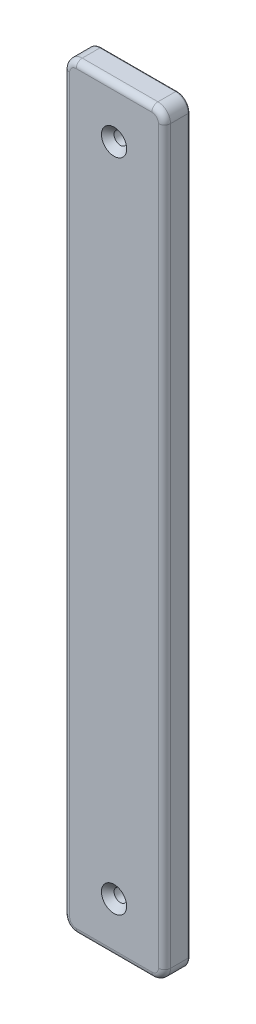
SolidWorks part; units mm, degrees
ref_plane "Front" through (0, 0, 0) normal (0, 0, 1) x (1, 0, 0)
ref_plane "Top" through (0, 0, 0) normal (0, 1, 0) x (1, 0, 0)
ref_plane "Right" through (0, 0, 0) normal (1, 0, 0) x (0, 0, -1)
sketch "Sketch1" plane through (0, 0, 0) normal (0, 0, 1) x (1, 0, 0)
  line L0 (0, 190.5) -> (0, -190.5) construction
  line L1 (25.4, -190.5) -> (-25.4, -190.5)
  line L2 (25.4, -190.5) -> (25.4, 190.5)
  line L3 (-25.4, 190.5) -> (25.4, 190.5)
  line L4 (-25.4, 190.5) -> (-25.4, -190.5)
  dimension "D1" = 381
  dimension "D3" = 50.8
extrude "Base-Extrude" add sketch "Sketch1" along normal blind 12.7
sketch "Sketch2" plane through (0, 0, 12.7) normal (0, 0, 1) x (1, 0, 0)
  line L0 (0, 0) -> (71.1, 0) construction
  line L1 (0, 190.5) -> (0, -190.5) construction
  line L2 (-25.4, 190.5) -> (25.4, 190.5) construction
  line L3 (25.4, -190.5) -> (-25.4, -190.5) construction
  circle A1 centre (0, -165.1) radius 3.175
  circle A3 centre (0, 165.1) radius 3.175
  dimension "D2" = 6.35
  dimension "D1" = 330.2
extrude "Cut-Extrude1" cut sketch "Sketch2" against normal through all
chamfer "Chamfer1" distance 3.175 angle 45 2 edges at (3.175, 165.1, 12.7) (3.175, -165.1, 12.7)
fillet "Fillet1" radius 6.35 4 edges at (25.4, -190.5, 6.35) (-25.4, -190.5, 6.35) (-25.4, 190.5, 6.35) (25.4, 190.5, 6.35)
fillet "Fillet2" radius 3.048 8 edges at (-23.5401, 188.6401, 12.7) (0, 190.5, 12.7) (23.5401, 188.6401, 12.7) (25.4, 0, 12.7) (23.5401, -188.6401, 12.7) (0, -190.5, 12.7) (-23.5401, -188.6401, 12.7) (-25.4, 0, 12.7)
shell "Shell1" thickness 1.524
ref_plane "Plane1" through (0, 0, 1.524) normal (0, 0, -1) x (-1, 0, 0)
sketch "Sketch3" plane through (0, 0, 1.524) normal (0, 0, -1) x (-1, 0, 0)
  line L0 (0, 165.1) -> (0, -165.1)
rib "Rib1" sketch "Sketch3" sketch "Sketch3" thickness 1.524 extrusion direction normal to sketch draft on yes draft angle 3 parameters "D1"=1.524, "D3"=3
fillet "Fillet3" radius 0.803 6 edges at (0, 160.401, 1.524) (0.762, 0, 1.524) (0, -160.401, 1.524) (0.956, -160.4993, 5.2249) (-0.762, 0, 1.524) (-0.956, -160.4993, 5.2249)
fillet "Fillet4" radius 0.762 16 edges at (25.4, 0, 0) (0, -190.5, 0) (-25.4, 0, 0) (0, 190.5, 0) (23.5401, 188.6401, 0) (-23.5401, 188.6401, 0) (-23.5401, -188.6401, 0) (23.5401, -188.6401, 0) (23.876, 0, 0) (-23.876, 0, 0) (22.4625, -187.5625, 0) (0, -188.976, 0) (-22.4625, -187.5625, 0) (-22.4625, 187.5625, 0) (0, 188.976, 0) (22.4625, 187.5625, 0)
fillet "Fillet5" radius 2.54 2 edges at (0, -169.799, 8.8937) (0, 169.799, 8.8937)
